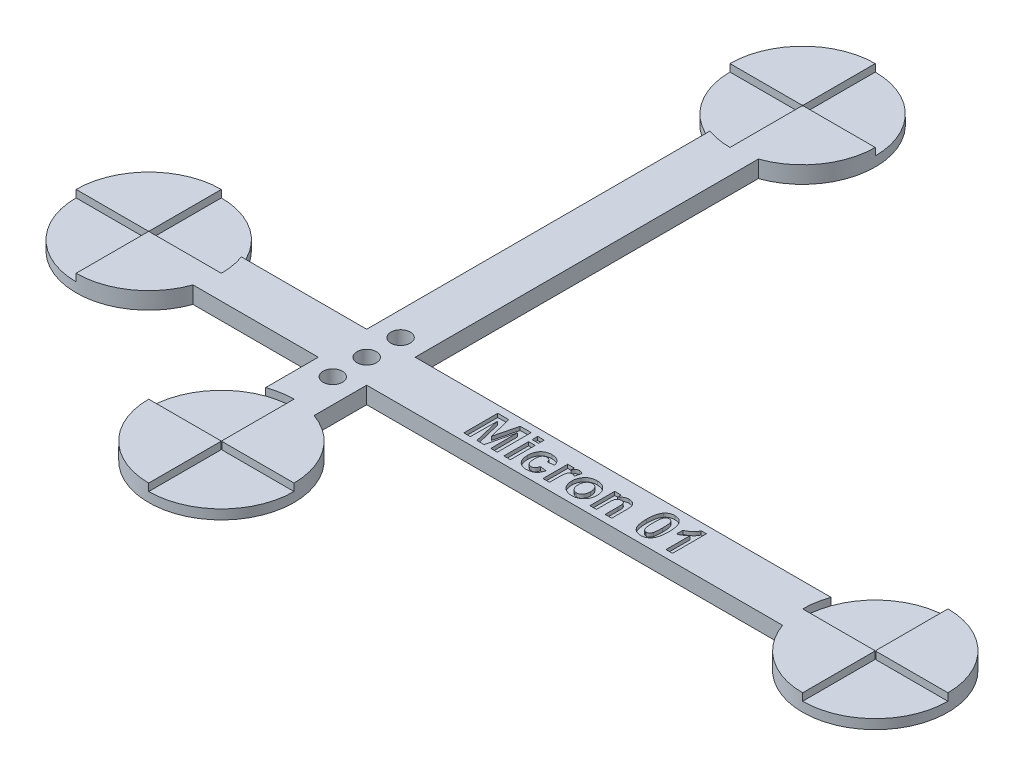
SolidWorks part; units mm, degrees
ref_plane "Front Plane" through (0, 0, 0) normal (0, 0, 1) x (1, 0, 0)
ref_plane "Top Plane" through (0, 0, 0) normal (0, 1, 0) x (1, 0, 0)
ref_plane "Right Plane" through (0, 0, 0) normal (1, 0, 0) x (0, 0, -1)
sketch "Sketch1" plane through (0, 0, 0) normal (0, 1, 0) x (1, 0, 0)
  line L0 (0, 0) -> (150, 0) construction
  line L1 (45, 90) -> (45, -30) construction
  line L2 (40, 75.8579) -> (40, 5)
  line L3 (50, 75.8579) -> (50, 5)
  line L4 (14.1421, 5) -> (40, 5)
  line L5 (14.1421, -5) -> (40, -5)
  line L6 (50, 5) -> (135.8579, 5)
  line L7 (40, -5) -> (40, -15.8579)
  line L8 (50, -5) -> (135.8579, -5)
  line L9 (50, -5) -> (50, -15.8579)
  arc A0 (14.1421, 5) -> (14.1421, -5) centre (0, 0) ccw
  arc A1 (135.8579, -5) -> (135.8579, 5) centre (150, 0) ccw
  arc A2 (50, 75.8579) -> (40, 75.8579) centre (45, 90) ccw
  arc A3 (40, -15.8579) -> (50, -15.8579) centre (45, -30) ccw
  dimension "D1" = 30
  dimension "D3" = 30
  dimension "D5" = 30
  dimension "D6" = 30
  dimension "D2" = 150
  dimension "D4" = 45
  dimension "D7" = 90
  dimension "D8" = 120
  dimension "D9" = 5
  dimension "D10" = 5
  dimension "D11" = 5
  dimension "D12" = 5
extrude "Boss-Extrude1" add sketch "Sketch1" along normal blind 3.5
sketch "Sketch2" plane through (0, 3.5, 0) normal (0, 1, 0) x (1, 0, 0)
  line L0 (45, -45) -> (45, -30.1)
  line L1 (-15, 0) -> (-0.1, 0)
  line L2 (30, 90) -> (44.9, 90)
  line L3 (0, 15) -> (0, 0.1)
  line L4 (150, 15) -> (150, 0.1)
  line L5 (30, -30) -> (44.9, -30)
  line L6 (45.1, 90) -> (60, 90)
  line L7 (45, 90.1) -> (45, 105)
  line L8 (45, 75) -> (45, 89.9)
  line L9 (45, -29.9) -> (45, -15)
  line L10 (45.1, -30) -> (60, -30)
  line L11 (135, 0) -> (149.9, 0)
  line L12 (0.1, 0) -> (15, 0)
  line L13 (0, -0.1) -> (0, -15)
  line L14 (150, -0.1) -> (150, -15)
  line L15 (150.1, 0) -> (165, 0)
  arc A0 (15, 0) -> (0, 15) centre (0, 0) ccw
  arc A1 (150, -15) -> (165, 0) centre (150, 0) ccw
  arc A2 (30, 90) -> (45, 75) centre (45, 90) ccw
  arc A3 (45, -15) -> (30, -30) centre (45, -30) ccw
  arc A4 (0, 0.1) -> (-0.1, 0) centre (0, 0) ccw
  arc A5 (45, 89.9) -> (45.1, 90) centre (45, 90) ccw
  arc A6 (149.9, 0) -> (150, -0.1) centre (150, 0) ccw
  arc A7 (44.9, -30) -> (45, -30.1) centre (45, -30) ccw
  arc A8 (45, 90.1) -> (44.9, 90) centre (45, 90) ccw
  arc A9 (60, 90) -> (45, 105) centre (45, 90) ccw
  arc A10 (45, -45) -> (60, -30) centre (45, -30) ccw
  arc A11 (45.1, -30) -> (45, -29.9) centre (45, -30) ccw
  arc A12 (-15, 0) -> (0, -15) centre (0, 0) ccw
  arc A13 (0, -0.1) -> (0.1, 0) centre (0, 0) ccw
  arc A14 (150.1, 0) -> (150, 0.1) centre (150, 0) ccw
  arc A15 (150, 15) -> (135, 0) centre (150, 0) ccw
  arc A16 (40, -15.8579) -> (50, -15.8579) centre (45, -30) ccw construction
  arc A17 (50, 75.8579) -> (40, 75.8579) centre (45, 90) ccw construction
  dimension "D1" = 0.2
  dimension "D2" = 0.2
  dimension "D3" = 0.2
  dimension "D4" = 0.2
extrude "Cut-Extrude1" cut sketch "Sketch2" against normal blind 1.52
sketch "Sketch3" plane through (0, 3.5, 0) normal (0, 1, 0) x (1, 0, 0)
  line L0 (45, -29.9) -> (45, -15) construction
  line L1 (45, 7) -> (45, -7) construction
  circle A0 centre (45, 0) radius 2
  circle A1 centre (45, 7) radius 2
  circle A2 centre (45, -7) radius 2
  point P2 (45, 0)
  dimension "D2" = 4
  dimension "D3" = 4
  dimension "D4" = 4
  dimension "D1" = 14
extrude "Cut-Extrude2" cut sketch "Sketch3" against normal through all
sketch "Sketch5" plane through (0, 3.5, 0) normal (0, 1, 0) x (1, 0, 0)
  line L0 (67.9289, -3.5) -> (117.9289, -3.5) construction
  line L1 (50, -5) -> (135.8579, -5) construction
  text T0 "Micron 01" font "Arial" height 7
  point P4 (92.9289, -3.5)
  point P5 (92.9289, -5)
  dimension "D1" = 1.5
  dimension "D2" = 50
extrude "Cut-Extrude3" cut sketch "Sketch5" against normal blind 0.75
